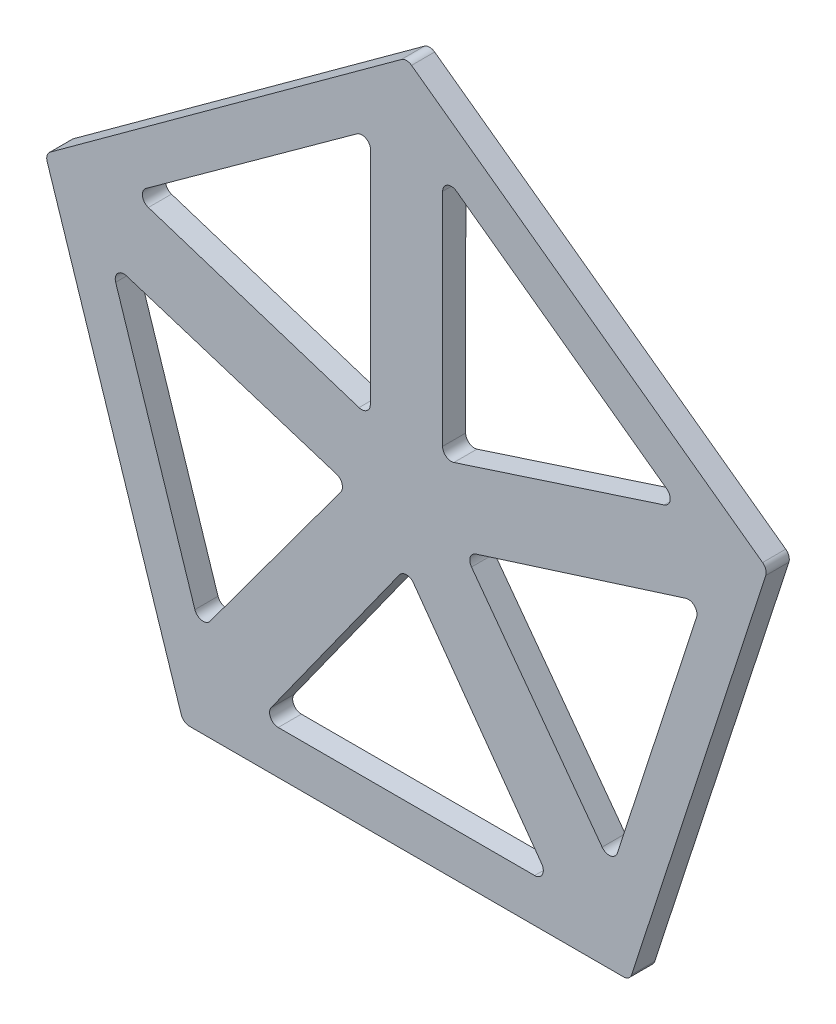
SolidWorks part; units mm, degrees
ref_plane "Front Plane" through (0, 0, 0) normal (0, 0, 1) x (1, 0, 0)
ref_plane "Top Plane" through (0, 0, 0) normal (0, 1, 0) x (1, 0, 0)
ref_plane "Right Plane" through (0, 0, 0) normal (1, 0, 0) x (0, 0, -1)
sketch "Model" plane through (0, 0, 0) normal (0, 0, 1) x (1, 0, 0)
  line L0 (-24.8652, 7.6558) -> (-15.5849, -20.8557)
  line L1 (-15.0144, -21.27) -> (15.0141, -21.27)
  line L2 (15.5847, -20.8554) -> (24.8653, 7.7054)
  line L3 (24.6473, 8.3762) -> (0.3531, 26.0235)
  line L4 (-0.3528, 26.023) -> (-24.6479, 8.3265)
  line L5 (-9.3602, -17.3207) -> (-0.4878, -4.9312)
  line L6 (0.4878, -4.9312) -> (9.3602, -17.3207)
  line L7 (8.8724, -18.27) -> (-8.8724, -18.27)
  line L8 (13.5426, -14.2326) -> (4.5013, -1.966)
  line L9 (4.8027, -1.0381) -> (19.3275, 3.5715)
  line L10 (20.0796, 2.8142) -> (14.5962, -14.062)
  line L11 (-19.3709, 3.5441) -> (-4.8461, -1.0655)
  line L12 (-4.5446, -1.9934) -> (-13.586, -14.26)
  line L13 (-14.6396, -14.0894) -> (-20.123, 2.7868)
  line L14 (-2.481, 19.5388) -> (-2.5003, 4.2651)
  line L15 (-3.2845, 3.695) -> (-17.8593, 8.3999)
  line L16 (-18.0269, 9.4569) -> (-3.4329, 20.0255)
  line L17 (17.8412, 8.4223) -> (3.2843, 3.6909)
  line L18 (2.4988, 4.2618) -> (2.5061, 19.5523)
  line L19 (3.4592, 20.0379) -> (18.0082, 9.4785)
  arc A0 (-15.5849, -20.8557) -> (-15.0144, -21.27) centre (-15.0144, -20.67) ccw
  arc A1 (15.0141, -21.27) -> (15.5847, -20.8554) centre (15.0141, -20.67) ccw
  arc A2 (24.8653, 7.7054) -> (24.6473, 8.3762) centre (24.2947, 7.8908) ccw
  arc A3 (0.3531, 26.0235) -> (-0.3528, 26.023) centre (0.0005, 25.538) ccw
  arc A4 (-24.6479, 8.3265) -> (-24.8652, 7.6558) centre (-24.2947, 7.8415) ccw
  arc A5 (0.4878, -4.9312) -> (-0.4878, -4.9312) centre (0, -5.2805) ccw
  arc A6 (8.8724, -18.27) -> (9.3602, -17.3207) centre (8.8724, -17.67) ccw
  arc A7 (-9.3602, -17.3207) -> (-8.8724, -18.27) centre (-8.8724, -17.67) ccw
  arc A8 (4.8027, -1.0381) -> (4.5013, -1.966) centre (4.9842, -1.61) ccw
  arc A9 (20.0796, 2.8142) -> (19.3275, 3.5715) centre (19.509, 2.9996) ccw
  arc A10 (13.5426, -14.2326) -> (14.5962, -14.062) centre (14.0256, -13.8766) ccw
  arc A11 (-4.5446, -1.9934) -> (-4.8461, -1.0655) centre (-5.0276, -1.6374) ccw
  arc A12 (-14.6396, -14.0894) -> (-13.586, -14.26) centre (-14.069, -13.904) ccw
  arc A13 (-19.3709, 3.5441) -> (-20.123, 2.7868) centre (-19.5524, 2.9722) ccw
  arc A14 (-3.2845, 3.695) -> (-2.5003, 4.2651) centre (-3.1002, 4.2659) ccw
  arc A15 (-18.0269, 9.4569) -> (-17.8593, 8.3999) centre (-17.6749, 8.9709) ccw
  arc A16 (-2.481, 19.5388) -> (-3.4329, 20.0255) centre (-3.081, 19.5395) ccw
  arc A17 (2.4988, 4.2618) -> (3.2843, 3.6909) centre (3.0988, 4.2615) ccw
  arc A18 (3.4592, 20.0379) -> (2.5061, 19.5523) centre (3.1065, 19.552) ccw
  arc A19 (17.8412, 8.4223) -> (18.0082, 9.4785) centre (17.6558, 8.9929) ccw
extrude "PCB Thickness" add sketch "Model" along normal blind 1.6 contours L4 A4 L0 A0 L1 A1 L2 A2 L3 A3 A19 L17 A17 L18 A18 L19 A16 L14 A14 L15 A15 L16 A13 L11 A11 L12 A12 L13 A10 L8 A8 L9 A9 L10 A7 L5 A5 L6 A6 L7 region at (0.0126, -0.051, 0)
